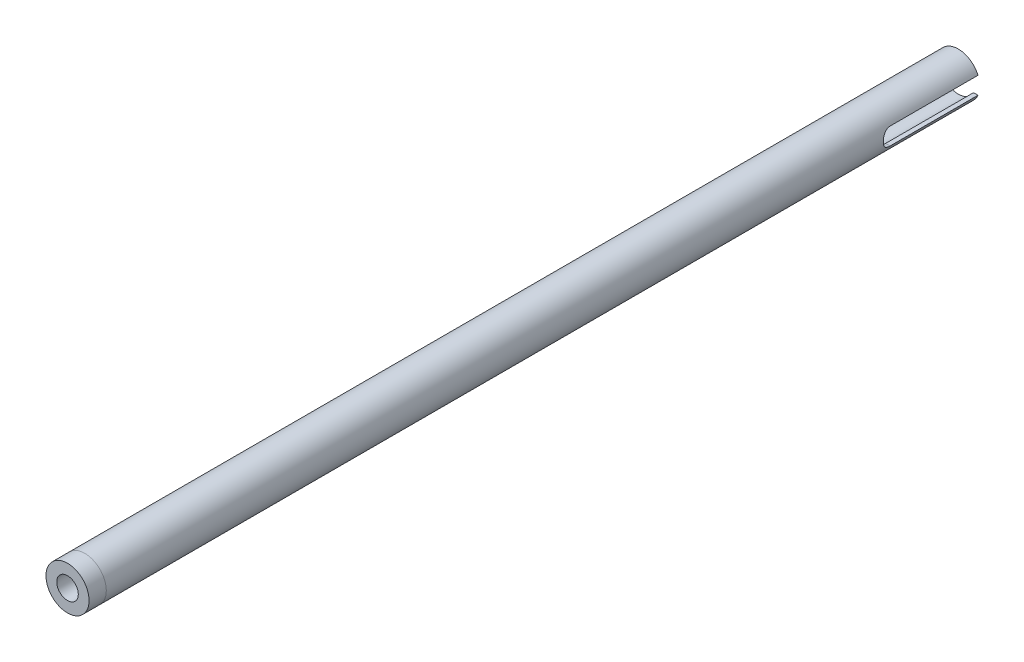
SolidWorks part; units mm, degrees
note: The reader was unsure of these and kept them because the rebuilt part matched: shared geometry of "Sketch1<3>", "Sketch1<4>", "Sketch1<5>".
material "AISI 4130 Steel, annealed at 865C"
ref_plane "Front Plane" through (0, 0, 0) normal (0, 0, 1) x (1, 0, 0)
ref_plane "Top Plane" through (0, 0, 0) normal (0, 1, 0) x (1, 0, 0)
ref_plane "Right Plane" through (0, 0, 0) normal (1, 0, 0) x (0, 0, -1)
sketch "Axis" plane through (0, 0, 0) normal (0, 1, 0) x (1, 0, 0)
  line L0 (0, 0) -> (0, 328.0702) construction
  line L1 (0, 0) -> (0, -28.575) construction
  line L2 (0, 328.0702) -> (-7.9375, 328.0702) construction
  line L4 (0, 356.4735) -> (-26.4371, 261.8721) construction
  dimension "D1" = 28.575
  dimension "D2" = 7.9375
sketch "Sketch1" plane through (0, 0, 0) normal (0, 0, 1) x (1, 0, 0)
  line L0 (-7.9375, 0) -> (7.9375, 0) construction
  line L1 (-7.2748, 3.175) -> (7.2748, 3.175)
  line L2 (-7.2748, -3.175) -> (7.2748, -3.175)
  circle A0 centre (0, 0) radius 7.9375
  circle A1 centre (0, 0) radius 6.4643
  circle A2 centre (0, 0) radius 3.9688
  dimension "D1" = 15.875
  dimension "D3" = 7.9375
  dimension "D2" = 1.4732
  dimension "D4" = 6.35
extrude "Threaded insert 1-1" add sketch "Sketch1" against normal blind 6.35 contours A2 L1 A1 | A1 L1 A0 | A2 L0 A1 L1 | A1 L0 A0 L1 | L0 A1 L2 A0 | L0 A2 L2 A1 | A2 L2 A1 | A1 L2 A0 | L0 A1 L2 A2 | L0 A0 L2 A1 | A0 L0 A1 L1 | A1 L0 A2 L1
extrude "Threaded insert 1-2" add sketch "Sketch1<3>" against normal blind 9.525 from surface at -6.35 contours A2 L1 A1 | A2 L0 A1 L1 | L0 A2 L2 A1 | A2 L2 A1 | L0 A1 L2 A2 | A1 L0 A2 L1 starting at face at (7.9375, 0, -6.35)
sketch "Sketch1<3>" plane through (0, 0, 0) normal (0, 0, 1) x (1, 0, 0) same geometry as "Sketch1"
extrude "A-arm tube" add sketch "Sketch1<4>" against normal up to vertex (328.0702 mm away) from surface at -6.35 separate body contours A1 L1 A0 | A1 L0 A0 L1 | L0 A1 L2 A0 | A1 L2 A0 | L0 A0 L2 A1 | A0 L0 A1 L1 starting at face at (6.4643, 0, -6.35)
sketch "Sketch1<4>" plane through (0, 0, 0) normal (0, 0, 1) x (1, 0, 0) same geometry as "Sketch1"
extrude "Apex slot" cut sketch "Sketch1<5>" along normal blind 35.56 from surface at -328.0702 contours A0 L0 A1 L1 | L0 A0 L2 A1 | A1 L0 A0 L1 | L0 A1 L2 A0 starting at face at (6.4643, 0, -328.0702)
sketch "Sketch1<5>" plane through (0, 0, 0) normal (0, 0, 1) x (1, 0, 0) same geometry as "Sketch1"
fillet "Fillet1" radius 3.175 4 edges at (-6.4528, 3.175, -292.5102) (-6.4528, -3.175, -292.5102) (6.4528, -3.175, -292.5102) (6.4528, 3.175, -292.5102)
equation "\"tube diameter\"= 5 / 8"
equation "\"tube thickness\"= .058"
equation "\"apex thickness\"= .25"
equation "\"tube slot\"= 1.4"
equation "\"D1@Sketch1\"=\"tube diameter\""
equation "\"D2@Sketch1\"=\"tube thickness\""
equation "\"threaded insert hole\"= .3125"
equation "\"D3@Sketch1\"=\"threaded insert hole\""
equation "\"D4@Sketch1\"=\"apex thickness\""
equation "\"D1@Apex slot\" = \"tube slot\""
equation "\"D1@Fillet1\"=\"apex thickness\"/2"
equation "\"D2@Axis\"=\"tube diameter\"/2"
